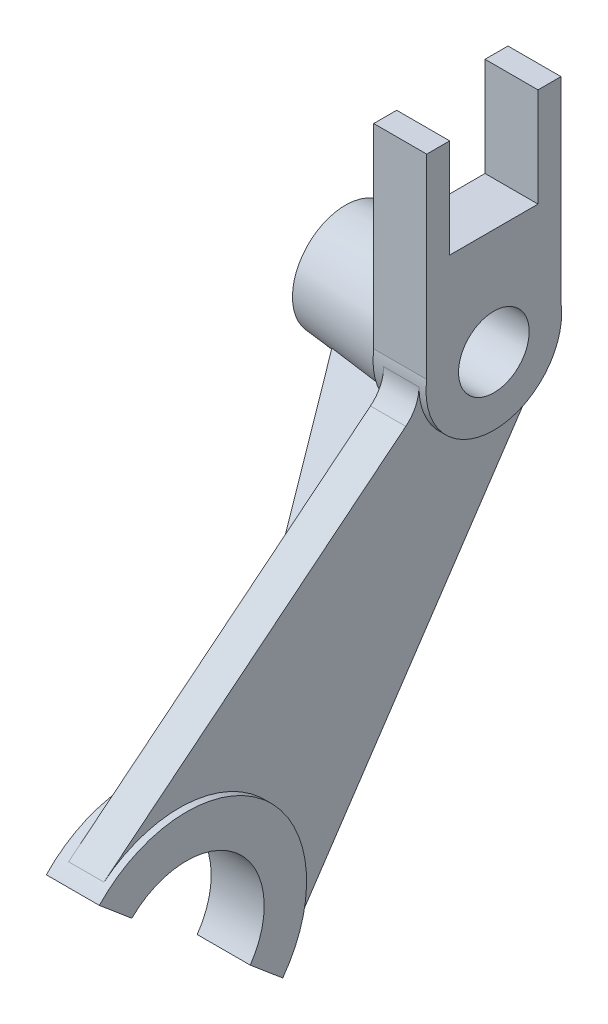
SolidWorks part; units mm, degrees
ref_plane "前视基准面" through (0, 0, 0) normal (0, 0, 1) x (1, 0, 0)
ref_plane "上视基准面" through (0, 0, 0) normal (0, 1, 0) x (1, 0, 0)
ref_plane "右视基准面" through (0, 0, 0) normal (1, 0, 0) x (0, 0, -1)
sketch "草图4" plane through (0, 0, 0) normal (1, 0, 0) x (0, 0, -1)
  line L0 (0, 0) -> (0, -27.361) construction
  line L1 (19, 0) -> (-19, 0)
  line L2 (19, 0) -> (19, 58)
  line L3 (19, 58) -> (-19, 58)
  line L4 (-19, 0) -> (-19, 58)
  dimension "D1" = 38
  dimension "D2" = 58
extrude "凸台-拉伸1" add sketch "草图4" against normal blind 15
sketch "草图2" plane through (0, 0, 0) normal (0, 0, 1) x (1, 0, 0)
  line L0 (-18.8659, 0) -> (16.1481, 0) construction
  line L1 (-42, 0) -> (-42, 15)
  line L2 (-42, 15) -> (0, 19.2)
  line L3 (0, 19.2) -> (0, 0)
  line L4 (-42, 0) -> (0, 0)
  line L5 (-42, 15) -> (-37, 15) construction
  line L6 (-37, 15) -> (-37, 15.5) construction
  dimension "D1" = 30
  dimension "D2" = 0.5
  dimension "D3" = 5
  dimension "D4" = 42
revolve "旋转1" add sketch "草图2" angle 360 about L0
sketch "草图5" plane through (0, 0, 0) normal (1, 0, 0) x (0, 0, -1)
  line L0 (0, 0) -> (-87, -103.2279) construction
  line L1 (-87, -103.2279) -> (-150.3066, -49.8734) construction
  line L2 (-111.6642, -79.8254) -> (-102.4638, -87.5795)
  line L3 (-68.9584, -115.8177) -> (-59.758, -123.5718)
  line L4 (-108.3604, -76.7754) -> (-22.9175, -7.7801)
  line L5 (-58.7565, -122.1568) -> (15.9493, -10.6892)
  line L6 (-111.6642, -79.8254) -> (-108.3604, -76.7754)
  line L7 (-59.758, -123.5718) -> (-58.7565, -122.1568)
  arc A0 (-19.2, 0) -> (15.9493, -10.6892) centre (0, 0) ccw
  arc A1 (-19, 2.7641) -> (19, 2.7641) centre (0, 0) ccw construction
  arc A2 (-59.758, -123.5718) -> (-112.9981, -81.3168) centre (-87, -103.2279) ccw construction
  arc A3 (-68.9584, -115.8177) -> (-102.4638, -87.5795) centre (-87, -103.2279) ccw
  arc A4 (-22.9175, -7.7801) -> (-19.2, 0) centre (-29.2, 0) ccw
  dimension "D3" = 68
  dimension "D4" = 44
  dimension "D6" = 20
  dimension "D1" = 135
  dimension "D2" = 87
  dimension "D5" = 2
extrude "凸台-拉伸2" add sketch "草图5" against normal blind 10 from offset 2 separate body offset against normal yes
sketch "草图6" plane through (0, 0, 0) normal (1, 0, 0) x (0, 0, -1)
  line L0 (-111.6642, -79.8254) -> (-102.4638, -87.5795) construction
  line L1 (-68.9584, -115.8177) -> (-59.758, -123.5718) construction
  line L2 (-111.6642, -79.8254) -> (-102.4638, -87.5795)
  line L3 (-68.9584, -115.8177) -> (-59.758, -123.5718)
  arc A0 (-59.758, -123.5718) -> (-112.9981, -81.3168) centre (-87, -103.2279) ccw construction
  arc A1 (-59.758, -123.5718) -> (-111.6642, -79.8254) centre (-87, -103.2279) ccw
  arc A2 (-68.9584, -115.8177) -> (-102.4638, -87.5795) centre (-87, -103.2279) ccw construction
  arc A3 (-68.9584, -115.8177) -> (-102.4638, -87.5795) centre (-87, -103.2279) ccw
extrude "凸台-拉伸3" add sketch "草图6" against normal blind 15
ref_axis "基准轴1" through (-15, -103.2279, 87) along (1, 0, 0)
ref_axis "基准轴2" through (0, 0, 0) along (-1, 0, 0)
ref_plane "基准面4" through (0, 0, 0) normal (0, 0.6444, 0.7647) x (1, 0, 0)
sketch "草图7" plane through (0, 0, 0) normal (0, 0.6444, 0.7647) x (1, 0, 0)
  line L0 (-32, -16) -> (-12, -85)
  line L1 (-42, -15) -> (0, -19.2) construction
  line L2 (-12, -20.7182) -> (-12, -128.5387) construction
  line L3 (-15, -133) -> (0, -133) construction
  dimension "D1" = 48
  dimension "D2" = 20
sketch "草图8" plane through (0, 0, 0) normal (1, 0, 0) x (0, 0, -1)
  circle A0 centre (0, 0) radius 19.2
extrude "凸台-拉伸4" add sketch "草图8" against normal blind 15
rib "筋4" sketch "草图7" sketch "草图7" thickness 10 extrusion direction parallel to sketch draft on yes draft angle 0.199 parameters "D1"=10, "D3"=0.199
sketch "草图9" plane through (-42, 0, 0) normal (-1, 0, 0) x (0, 0, 1)
  circle A0 centre (0, 0) radius 10
  dimension "D1" = 20
extrude "切除-拉伸1" cut sketch "草图9" against normal through all
sketch "草图10" plane through (-15, 0, 0) normal (-1, 0, 0) x (0, 0, 1)
  line L0 (-19, 58) -> (19, 58) construction
  line L1 (-12.5, 58) -> (12.5, 58)
  line L2 (-12.5, 58) -> (-12.5, 30)
  line L3 (-12.5, 30) -> (12.5, 30)
  line L4 (12.5, 58) -> (12.5, 30)
  line L5 (0, 0) -> (0, 27.3073) construction
  dimension "D1" = 25
  dimension "D2" = 30
extrude "切除-拉伸2" cut sketch "草图10" against normal through all
